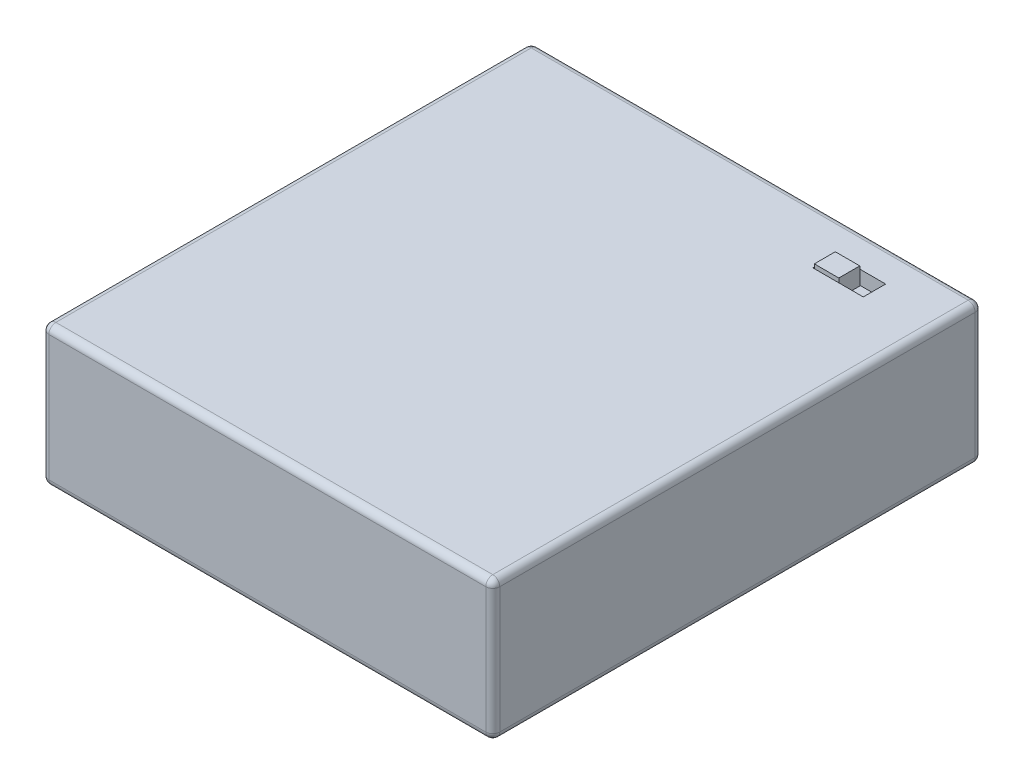
SolidWorks part; units mm, degrees
ref_plane "前视基准面" through (0, 0, 0) normal (0, 0, 1) x (1, 0, 0)
ref_plane "上视基准面" through (0, 0, 0) normal (0, 1, 0) x (1, 0, 0)
ref_plane "右视基准面" through (0, 0, 0) normal (1, 0, 0) x (0, 0, -1)
other "Configuration Table"
sketch "草图1" plane through (0, 0, 0) normal (0, 1, 0) x (1, 0, 0)
  line L1 (-32.25, -35) -> (32.25, -35)
  line L2 (-32.25, -35) -> (-32.25, 35)
  line L3 (-32.25, 35) -> (32.25, 35)
  line L4 (32.25, -35) -> (32.25, 35)
  line L5 (-32.25, -35) -> (32.25, 35) construction
  line L6 (-32.25, 35) -> (32.25, -35) construction
  line L19 (16.25, 30) -> (19.75, 30)
  line L20 (16.25, 30) -> (16.25, 27)
  line L29 (16.25, 27) -> (19.75, 27)
  line L30 (19.75, 30) -> (19.75, 27)
  line L31 (16.15, 30.1) -> (23.35, 30.1)
  line L32 (16.15, 30.1) -> (16.15, 26.9)
  line L33 (16.15, 26.9) -> (23.35, 26.9)
  line L34 (23.35, 30.1) -> (23.35, 26.9)
  point P0 (0, 0)
  point P14 (16.15, 28.5)
  point P15 (16.25, 28.5)
  dimension "D1" = 70
  dimension "D2" = 8
  dimension "D7" = 0.1
  dimension "D5" = 16
  dimension "D6" = 3.5
  dimension "D3" = 64.5
  dimension "D4" = 3
  dimension "D8" = 0.1
  dimension "D9" = 7.2
extrude "凸台-拉伸1" add sketch "草图1" along normal blind 20 contours L4 L3 L2 L1
fillet "圆角1" radius 1 12 edges at (32.25, 10, -35) (32.25, 10, 35) (-32.25, 10, -35) (-32.25, 10, 35) (0, 0, -35) (0, 20, -35) (0, 20, 35) (0, 0, 35) (32.25, 0, 0) (32.25, 20, 0) (-32.25, 0, 0) (-32.25, 20, 0)
extrude "切除-拉伸1" cut sketch "草图1<9>" against normal blind 2 from surface contours L31 L34 L33 L32 starting at face at (0, 20, 0)
sketch "草图1<9>" plane through (0, 0, 0) normal (0, 1, 0) x (1, 0, 0) same geometry as "草图1"
extrude "凸台-拉伸2" add sketch "草图1<10>" along normal blind 2.5 from surface contours L30 L29 L20 L19 starting at face at (19.75, 18, -28.5)
sketch "草图1<10>" plane through (0, 0, 0) normal (0, 1, 0) x (1, 0, 0) same geometry as "草图1"
sketch "草图2" plane through (0, 0, -35) normal (0, 0, -1) x (-1, 0, 0)
  line L0 (-31.25, 20) -> (31.25, 20) construction
  line L1 (32.25, 19) -> (32.25, 1) construction
  circle A0 centre (25.25, 15) radius 2.5
  dimension "D3" = 5
  dimension "D1" = 5
  dimension "D2" = 7
extrude "切除-拉伸2" cut sketch "草图2" against normal blind 2 contours A0
